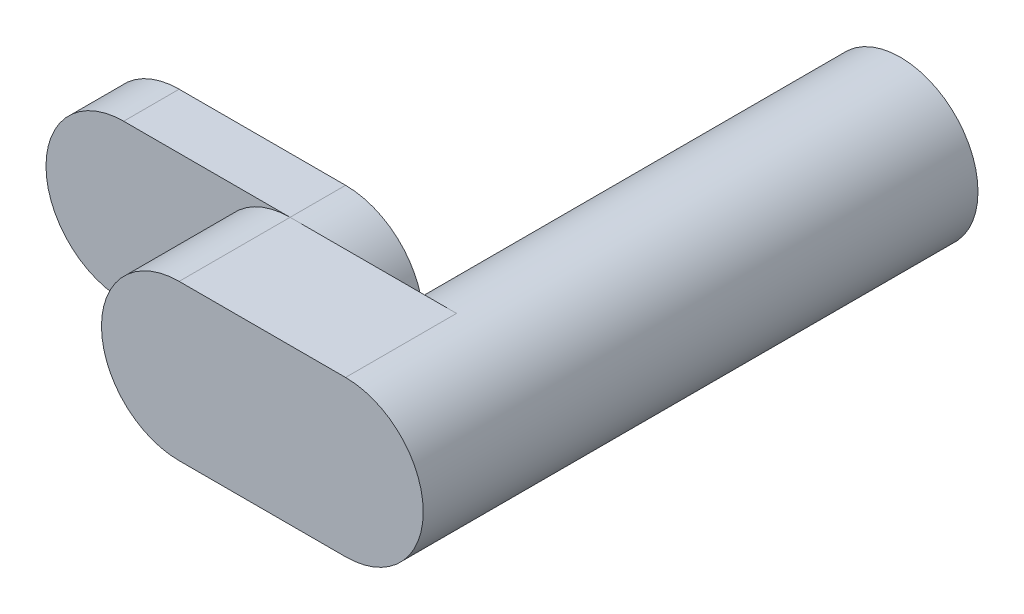
SolidWorks part; units mm, degrees
ref_plane "Płaszczyzna przednia" through (0, 0, 0) normal (0, 0, 1) x (1, 0, 0)
ref_plane "Płaszczyzna górna" through (0, 0, 0) normal (0, 1, 0) x (1, 0, 0)
ref_plane "Płaszczyzna prawa" through (0, 0, 0) normal (1, 0, 0) x (0, 0, -1)
sketch "Szkic1" plane through (0, 0, 0) normal (0, 0, 1) x (1, 0, 0)
  circle A0 centre (0, 0) radius 70
extrude "Dodanie-wyciągnięcie1" add sketch "Szkic1" along normal blind 400
sketch "Szkic2" plane through (0, 0, 400) normal (0, 0, 1) x (1, 0, 0)
  line L0 (0, 0) -> (-150, 0) construction
  line L1 (0, -70) -> (-150, -70)
  line L2 (0, 70) -> (-150, 70)
  arc A0 (0, -70) -> (0, 70) centre (0, 0) ccw
  arc A1 (-150, 70) -> (-150, -70) centre (-150, 0) ccw
  point P3 (-75, 0)
  dimension "D2" = 70
  dimension "D1" = 150
extrude "Dodanie-wyciągnięcie2" add sketch "Szkic2" along normal blind 100
sketch "Szkic3" plane through (0, 0, 400) normal (0, 0, -1) x (-1, 0, 0)
  line L0 (150, 0) -> (300, 0) construction
  line L1 (150, 70) -> (300, 70)
  line L2 (150, -70) -> (300, -70)
  arc A0 (150, 70) -> (150, -70) centre (150, 0) ccw
  arc A1 (300, -70) -> (300, 70) centre (300, 0) ccw
  point P2 (225, 0)
  dimension "D1" = 70
  dimension "D2" = 150
extrude "Dodanie-wyciągnięcie3" add sketch "Szkic3" along normal blind 50
ref_axis "Oś1" through (0, 0, 736.1177) along (0, 0, -1)
sketch "Szkic4" plane through (0, 0, 0) normal (0, 0, -1) x (-1, 0, 0)
  point P0 (0, 0)
sketch "Szkic6" plane through (0, 0, 0) normal (0, 1, 0) x (1, 0, 0)
  line L0 (0, -736.1177) -> (0, 171.1786) construction
  line L1 (0, -500) -> (70, -500) construction
  line L2 (-370, -400) -> (-300, -400) construction
  point P0 (0, -450)
  point P5 (-335, -450)
  point P6 (0, 0)
  point P9 (-335, -400)
  point P10 (0, 0)
  dimension "D1" = 50
